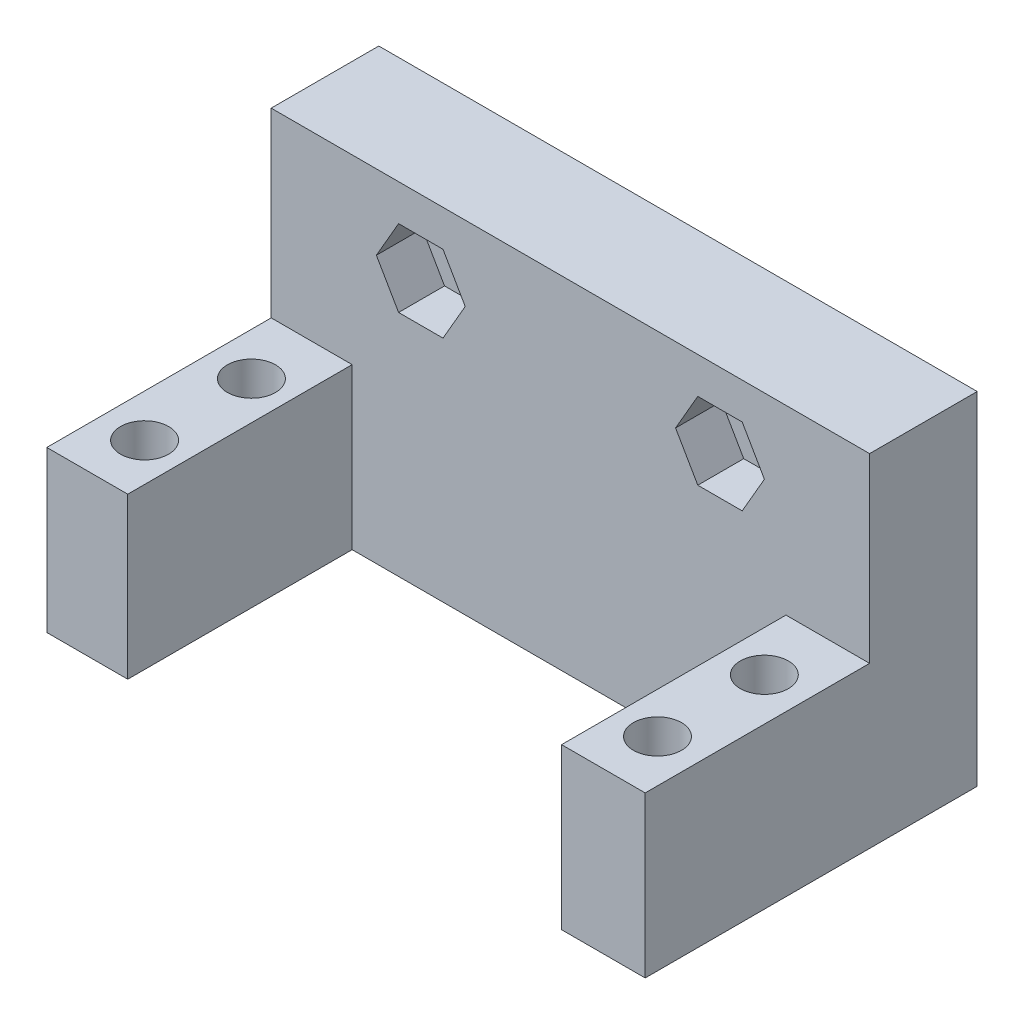
SolidWorks part; units mm, degrees
ref_plane "Płaszczyzna przednia" through (0, 0, 0) normal (0, 0, 1) x (1, 0, 0)
ref_plane "Płaszczyzna górna" through (0, 0, 0) normal (0, 1, 0) x (1, 0, 0)
ref_plane "Płaszczyzna prawa" through (0, 0, 0) normal (1, 0, 0) x (0, 0, -1)
sketch "Szkic1" plane through (0, 0, 0) normal (0, 0, 1) x (1, 0, 0)
  line L0 (14, 0) -> (-14, 0)
  line L2 (20, -7) -> (-20, -7)
  line L3 (20, -7) -> (20, 7)
  line L4 (20, 7) -> (-20, 7)
  line L5 (-20, -7) -> (-20, 7)
  line L6 (20, -7) -> (-20, 7) construction
  line L7 (20, 7) -> (-20, -7) construction
  circle A0 centre (-14, 0) radius 2
  circle A1 centre (14, 0) radius 2
  point P4 (0, 0)
  point P7 (0, 0)
extrude "Dodanie-wyciągnięcie1" add sketch "Szkic1" along normal blind 10.77 contours L5 L2 L3 L4 A1 A0 region at (0, -6.5762, 0)
sketch "Szkic2" plane through (0, 0, 10.77) normal (0, 0, 1) x (1, 0, 0)
  line L1 (28, -7) -> (-28, -7)
  line L2 (28, -7) -> (28, 7)
  line L3 (28, 7) -> (-28, 7)
  line L4 (-28, -7) -> (-28, 7)
  line L5 (28, -7) -> (-28, 7) construction
  line L6 (28, 7) -> (-28, -7) construction
  point P0 (0, 0)
extrude "Dodanie-wyciągnięcie2" add sketch "Szkic2" along normal blind 20.3
sketch "Szkic5" plane through (0, 7, 0) normal (0, 1, 0) x (1, 0, 0)
  line L0 (-28, -20.92) -> (0, -20.92)
  line L5 (-28, -31.07) -> (-28, -10.77) construction
  line L6 (0, -20.92) -> (0, -15.92)
  line L7 (0, -15.92) -> (-24, -15.92)
  circle A0 centre (-24, -15.92) radius 2.25
  circle A1 centre (24, -15.92) radius 2.25
  circle A2 centre (24, -25.92) radius 2.25
  circle A3 centre (-24, -25.92) radius 2.25
  dimension "D1" = 2
  dimension "D2" = 2
extrude "Wytnij-wyciągnięcie2" cut sketch "Szkic5" against normal up to surface (14 mm away) contours A2 | A1 | A3 | A0 region at (-26.1864, 7, 15.92) region at (24, 7, 15.92) region at (24, 7, 25.92) region at (-24, 7, 25.92) up to face at (0, -7, 13.1525)
sketch "Szkic8" plane through (0, 7, 0) normal (0, 1, 0) x (1, 0, 0)
  line L1 (-28, -10.77) -> (28, -10.77)
  line L2 (-28, -10.77) -> (-28, 0)
  line L3 (-28, 0) -> (28, 0)
  line L4 (28, -10.77) -> (28, 0)
extrude "Dodanie-wyciągnięcie3" add sketch "Szkic8" against normal up to surface (14 mm away) up to face at (26.25, -7, 15.92)
sketch "Szkic6" plane through (0, 7, 0) normal (0, 1, 0) x (1, 0, 0)
  line L0 (-0.1249, -31.07) -> (-21.1249, -31.07)
  line L2 (28, -31.07) -> (-28, -31.07) construction
  line L4 (-21.1249, -31.07) -> (20.8751, -31.07)
  line L5 (-21.1249, -31.07) -> (-21.1249, -10.07)
  line L6 (-21.1249, -10.07) -> (20.8751, -10.07)
  line L7 (20.8751, -31.07) -> (20.8751, -10.07)
  point P5 (-0.1249, -31.07)
  line M15 (-28, -31.07) -> (28, -31.07)
extrude "Wytnij-wyciągnięcie3" cut sketch "Szkic6" along direction (0, -1, 0) on the side against the normal blind 21 contours L7 L5 M15 | L7 L6 L5 region at (-0.1249, 7, 20.57)
sketch "Szkic12" plane through (0, -7, 0) normal (0, -1, 0) x (1, 0, 0)
  line L1 (-28, 0) -> (28, 0)
  line L2 (-28, 0) -> (-28, 31.07)
  line L3 (-28, 31.07) -> (28, 31.07)
  line L4 (28, 0) -> (28, 31.07)
  line L5 (20.8751, 31.07) -> (-21.1249, 31.07)
  line L6 (20.8751, 31.07) -> (20.8751, 10.07)
  line L7 (20.8751, 10.07) -> (-21.1249, 10.07)
  line L8 (-21.1249, 31.07) -> (-21.1249, 10.07)
  circle A0 centre (-24, 25.92) radius 2.25
  circle A1 centre (-24, 15.92) radius 2.25
  circle A2 centre (24, 25.92) radius 2.25
  circle A3 centre (24, 15.92) radius 2.25
  circle M1 centre (24, 15.92) radius 2.25
  circle M2 centre (-24, 25.92) radius 2.25
  circle M3 centre (-24, 15.92) radius 2.25
  circle M4 centre (24, 25.92) radius 2.25
  line M5 (20.8751, 10.07) -> (-21.1249, 10.07)
  line M6 (-21.1249, 10.07) -> (-21.1249, 31.07)
  line M7 (-21.1249, 31.07) -> (-28, 31.07)
  line M8 (-28, 31.07) -> (-28, 0)
  line M9 (-28, 0) -> (28, 0)
  line M10 (28, 0) -> (28, 31.07)
  line M11 (28, 31.07) -> (20.8751, 31.07)
  line M12 (20.8751, 31.07) -> (20.8751, 10.07)
extrude "Dodanie-wyciągnięcie4" add sketch "Szkic12" along normal blind 18 contours M12 M5 M6 M7 M8 M9 M10 M11 M2 M4 M3 M1 region at (0.1387, -7, 9.5128)
sketch "Szkic4" plane through (0, 0, 10.77) normal (0, 0, 1) x (1, 0, 0)
  line L1 (-16.0785, 3.6) -> (-18.1569, 0)
  line L2 (-18.1569, 0) -> (-16.0785, -3.6)
  line L3 (-16.0785, -3.6) -> (-11.9215, -3.6)
  line L4 (-11.9215, -3.6) -> (-9.8431, 0)
  line L5 (-9.8431, 0) -> (-11.9215, 3.6)
  line L6 (-11.9215, 3.6) -> (-16.0785, 3.6)
  line L7 (11.9215, 3.6) -> (9.8431, 0)
  line L8 (9.8431, 0) -> (11.9215, -3.6)
  line L9 (11.9215, -3.6) -> (16.0785, -3.6)
  line L10 (16.0785, -3.6) -> (18.1569, 0)
  line L11 (18.1569, 0) -> (16.0785, 3.6)
  line L12 (16.0785, 3.6) -> (11.9215, 3.6)
  line L13 (-20, -7) -> (-20, 7) construction
  line L14 (-20, 3.6) -> (-20, -3.6)
  line L17 (20, -7) -> (20, 7) construction
  line L18 (20, -3.6) -> (20, 3.6)
  circle A0 centre (-14, 0) radius 3.6 construction
  circle A1 centre (14, 0) radius 3.6 construction
extrude "Wytnij-wyciągnięcie1" cut sketch "Szkic4" against normal blind 5 contours L5 L6 L1 L2 L3 L4 | L11 L12 L7 L8 L9 L10 region at (-14, 0, 10.77) region at (14, 0, 10.77)
sketch "Szkic9" plane through (0, 0, 10.07) normal (0, 0, 1) x (1, 0, 0)
  line L0 (-14, 0) -> (14, 0)
  circle A0 centre (-14, 0) radius 2.2
  circle A1 centre (14, 0) radius 2.2
extrude "Wytnij-wyciągnięcie4" cut sketch "Szkic9" against normal blind 21 contours A1 | A0 region at (14, 2.1378, 10.07) region at (-16.1378, 0, 10.07)
sketch "Szkic10" plane through (0, 7, 0) normal (0, 1, 0) x (1, 0, 0)
  line L0 (-28, -31.07) -> (-28, 0) construction
  line L1 (28, -31.07) -> (-28, -31.07)
  line L2 (28, -31.07) -> (28, -10.07)
  line L3 (28, -10.07) -> (-28, -10.07)
  line L4 (-28, -31.07) -> (-28, -10.07)
extrude "Wytnij-wyciągnięcie5" cut sketch "Szkic10" against normal blind 17
sketch "Szkic13" plane through (-21.1249, 0, 0) normal (1, 0, 0) x (0, 0, -1)
  line L1 (-31.07, -25) -> (-10.07, -25)
  line L2 (-31.07, -25) -> (-31.07, -10)
  line L3 (-31.07, -10) -> (-10.07, -10)
  line L4 (-10.07, -25) -> (-10.07, -10)
extrude "Dodanie-wyciągnięcie5" add sketch "Szkic13" along normal blind 0.7
sketch "Szkic16" plane through (20.8751, 0, 0) normal (-1, 0, 0) x (0, 0, 1)
  line L1 (31.07, -10) -> (10.07, -10)
  line L2 (31.07, -10) -> (31.07, -25)
  line L3 (31.07, -25) -> (10.07, -25)
  line L4 (10.07, -10) -> (10.07, -25)
extrude "Dodanie-wyciągnięcie7" add sketch "Szkic16" along normal blind 0.7
